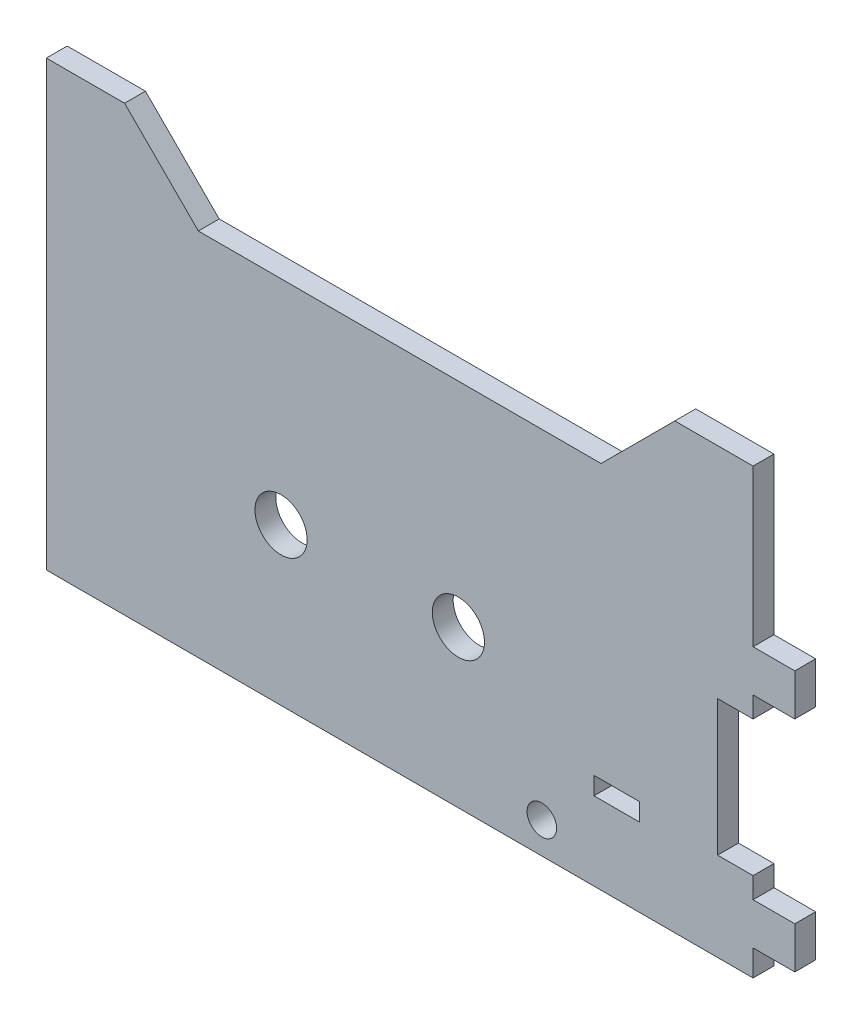
SolidWorks part; units mm, degrees
ref_plane "Front Plane" through (0, 0, 0) normal (0, 0, 1) x (1, 0, 0)
ref_plane "Top Plane" through (0, 0, 0) normal (0, 1, 0) x (1, 0, 0)
ref_plane "Right Plane" through (0, 0, 0) normal (1, 0, 0) x (0, 0, -1)
sketch "Sketch1" plane through (0, 0, 0) normal (0, 0, 1) x (1, 0, 0)
  line L0 (49, 30) -> (56.5, 30)
  line L1 (-79, -30) -> (49, -30)
  line L2 (-79, -30) -> (-79, 30)
  line L3 (-79, 30) -> (49, 30)
  line L6 (56.5, 13) -> (49.7, 13)
  line L7 (49.7, 13) -> (49.7, -13)
  line L8 (49.7, -13) -> (56.5, -13)
  line L10 (56.5, -30) -> (49, -30)
  line L11 (56.5, 30) -> (56.5, 13) construction
  line L12 (56.5, -13) -> (56.5, -30) construction
  line L13 (56.5, 30) -> (56.5, 25)
  line L14 (56.5, 25) -> (64.5, 25)
  line L15 (64.5, 25) -> (64.5, 17)
  line L16 (64.5, 17) -> (56.5, 17)
  line L17 (56.5, 17) -> (56.5, 13)
  line L18 (56.5, -13) -> (56.5, -17)
  line L19 (56.5, -17) -> (64.5, -17)
  line L20 (64.5, -17) -> (64.5, -25)
  line L21 (64.5, -25) -> (56.5, -25)
  line L22 (56.5, -25) -> (56.5, -30)
  line L23 (49, 30) -> (49, -30) construction
  line L24 (26, -11.6) -> (34.7, -11.6)
  line L25 (26, -11.6) -> (26, -15)
  line L26 (26, -15) -> (34.7, -15)
  line L27 (34.7, -11.6) -> (34.7, -15)
  circle A0 centre (0, 0) radius 5
  circle A3 centre (-34, 0) radius 5
  circle A4 centre (16, -24) radius 2.83
  point P1 (0, 0)
  dimension "D3" = 128
  dimension "D4" = 6
  dimension "D5" = 10
  dimension "D1" = 45
  dimension "D7" = 5
  dimension "D17" = 5.66
  dimension "D18" = 95
  dimension "D19" = 30
  dimension "D22" = 10
  dimension "D6" = 34
  dimension "D8" = 26
  dimension "D9" = 5
  dimension "D10" = 7.5
  dimension "D11" = 8
  dimension "D12" = 8
  dimension "D13" = 8.7
  dimension "D14" = 3.4
  dimension "D15" = 15
  dimension "D16" = 15
  dimension "D20" = 4
  dimension "D21" = 4
  dimension "D23" = 30
  dimension "D24" = 8
extrude "Boss-Extrude1" add sketch "Sketch1" along normal blind 4
sketch "Sketch2" plane through (0, 0, 0) normal (0, 0, 1) x (1, 0, 0)
  line L0 (-79, 30) -> (56.5, 30)
  line L1 (56.5, 30) -> (56.5, 55)
  line L2 (56.5, 55) -> (41.5, 55)
  line L3 (41.5, 55) -> (27.3579, 40.8579)
  line L4 (27.3579, 40.8579) -> (-49.8579, 40.8579)
  line L5 (-49.8579, 40.8579) -> (-64, 55)
  line L6 (-64, 55) -> (-79, 55)
  line L7 (-79, 55) -> (-79, 30)
  dimension "D1" = 25
  dimension "D2" = 15
  dimension "D3" = 20
  dimension "D4" = 135
extrude "Boss-Extrude2" add sketch "Sketch2" along normal blind 4
